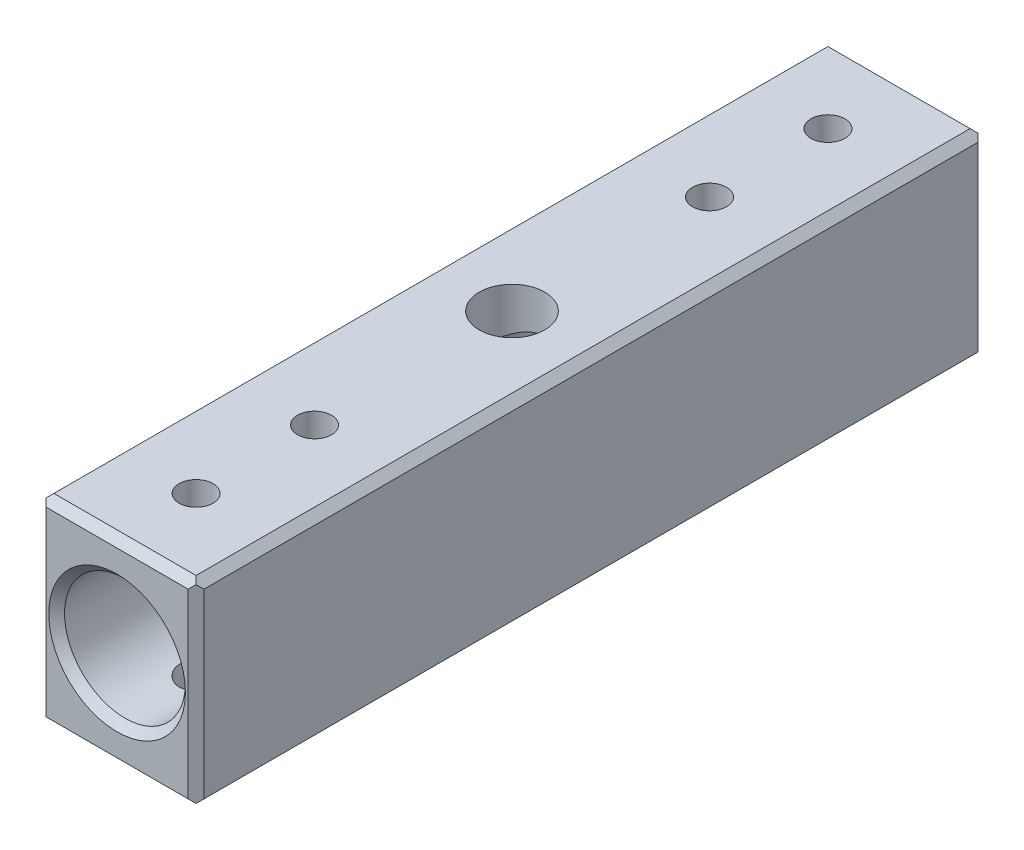
SolidWorks part; units mm, degrees
material "ABS"
ref_plane "前视基准面" through (0, 0, 0) normal (0, 0, 1) x (1, 0, 0)
ref_plane "上视基准面" through (0, 0, 0) normal (0, 1, 0) x (1, 0, 0)
ref_plane "右视基准面" through (0, 0, 0) normal (1, 0, 0) x (0, 0, -1)
other "Configuration Table"
sketch "草图2" plane through (0, 0, 0) normal (0, 0, 1) x (1, 0, 0)
  line L11 (-10, 12.5) -> (10, 12.5)
  line L12 (-10, 12.5) -> (-10, -12.5)
  line L13 (-10, -12.5) -> (10, -12.5)
  line L14 (10, 12.5) -> (10, -12.5)
  line L15 (0, -12.5) -> (0, 12.5) construction
  line L16 (-10, 0) -> (10, 0) construction
  circle A0 centre (0, 0) radius 7.65
  point P0 (0, 0)
  dimension "D1" = 15.3
  dimension "D4" = 25
  dimension "D5" = 20
extrude "凸台-拉伸1" add sketch "草图2" against normal blind 100
sketch "草图3" plane through (0, 12.5, 0) normal (0, 1, 0) x (1, 0, 0)
  line L0 (0, 100) -> (0, 0) construction
  line L1 (0, 25) -> (0, 75) construction
  line L2 (-10, 50) -> (10, 50) construction
  line L4 (-10, 0) -> (10, 0)
  line L5 (10, 0) -> (10, 100)
  line L6 (10, 100) -> (-10, 100)
  line L7 (-10, 100) -> (-10, 0)
  line L8 (-10, 0) -> (10, 0)
  line L9 (10, 0) -> (10, 100)
  line L10 (10, 100) -> (-10, 100)
  line L11 (-10, 100) -> (-10, 0)
  circle A0 centre (0, 75) radius 2.15
  circle A2 centre (0, 50) radius 4.15
  circle A3 centre (0, 90) radius 2.15
  circle A4 centre (0, 10) radius 2.15
  circle A5 centre (0, 25) radius 2.15
  point P10 (0, 50)
  dimension "D2" = 4.3
  dimension "D3" = 15
  dimension "D5" = 8.3
  dimension "D4" = 25
  dimension "D1" = 0
extrude "切除-拉伸2" cut sketch "草图3" against normal through all contours A2 | A0 | A3 | A5 | A4 region at (0, 12.5, -75) region at (0, 12.5, -50) region at (0, 12.5, -90) region at (0, 12.5, -10) region at (0, 12.5, -25)
sketch "草图5" plane through (10, 0, 0) normal (1, 0, 0) x (0, 0, -1)
  line L0 (0, 0) -> (100, 0) construction
  line L1 (0, -12.5) -> (0, 12.5) construction
  line L2 (100, -12.5) -> (100, 12.5) construction
  line L3 (50, 12.5) -> (50, -12.5) construction
  line L4 (100, 12.5) -> (0, 12.5) construction
  line L5 (100, -12.5) -> (0, -12.5) construction
  circle A0 centre (10, 0) radius 2.15
  circle A1 centre (90, 0) radius 2.15
  dimension "D1" = 4.3
  dimension "D2" = 10
chamfer "倒角1" distance 1 angle 45 10 edges at (0, 12.5, -100) (-10, 0, -100) (0, -12.5, -100) (10, 0, -100) (0, -12.5, 0) (-10, 0, 0) (0, 12.5, 0) (10, 0, 0) (7.65, 0, -100) (7.65, 0, 0)
chamfer "倒角2" distance 1 angle 45 4 edges at (10, -12.5, -50) (-10, -12.5, -50) (10, 12.5, -50) (-10, 12.5, -50)
